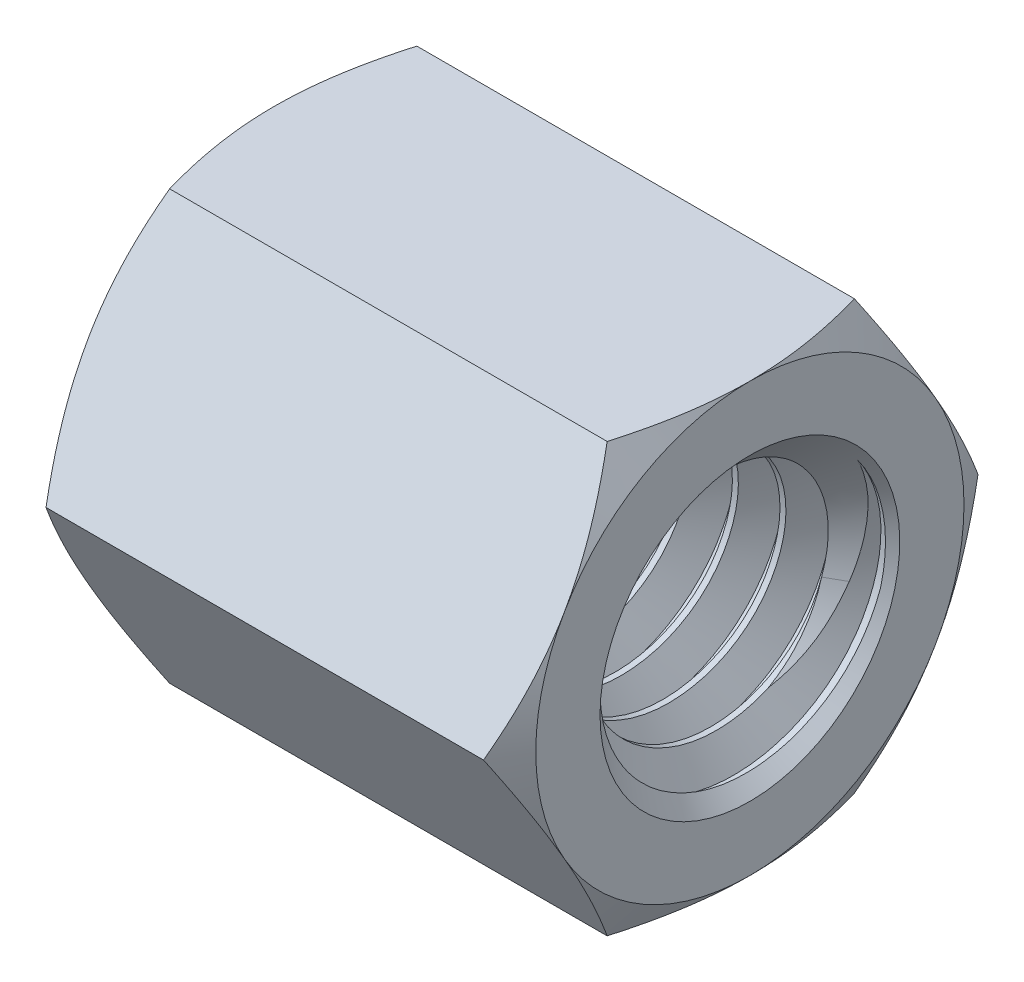
SolidWorks part; units mm, degrees
note: '?' marks a value the reader was unsure of.
ref_plane "Front Plane" through (0, 0, 0) normal (0, 0, 1) x (1, 0, 0)
ref_plane "Top Plane" through (0, 0, 0) normal (0, 1, 0) x (1, 0, 0)
ref_plane "Right Plane" through (0, 0, 0) normal (1, 0, 0) x (0, 0, -1)
sketch "Sketch1" plane through (0, 0, 0) normal (0, 0, 1) x (1, 0, 0)
  line L0 (0, 0) -> (5, 0) construction
  line L1 (0, 2.25) -> (0, -2.25) construction
  line L3 (0, 1.5) -> (-0.5, 1.5) construction
  line L4 (0, 2.25) -> (5, 2.25) construction
  point P6 (0, 0)
  dimension "Hex" = 4.5
  dimension "Pitch" = 0.5
  dimension "Thread OD" = 3
  dimension "Length" = 5
sketch "Sketch2" plane through (0, 0, 0) normal (1, 0, 0) x (0, 0, -1)
  line L0 (0, 0) -> (-1.0607, -1.0607) construction
  line L1 (1.299, 2.25) -> (-1.299, 2.25)
  line L2 (-1.299, 2.25) -> (-2.5981, 0)
  line L3 (-2.5981, 0) -> (-1.299, -2.25)
  line L4 (-1.299, -2.25) -> (1.299, -2.25)
  line L5 (1.299, -2.25) -> (2.5981, 0)
  line L6 (2.5981, 0) -> (1.299, 2.25)
  circle A0 centre (0, 0) radius 2.25 construction
  circle A1 centre (0, 0) radius 1.5 construction
  dimension "D1" = 45
extrude "Boss-Extrude1" add sketch "Sketch2" along normal up to vertex (5 mm away) up to point (5, 0, 0)
sketch "Sketch3" plane through (0, 0, 0) normal (0, 0, 1) x (1, 0, 0)
  line L0 (0, 1.575) -> (0.075, 1.5)
  line L1 (0, 0) -> (5, 0)
  line L2 (0, 0) -> (0, 1.575)
  line L3 (0.075, 1.5) -> (4.925, 1.5)
  line L4 (5, 0) -> (5, 1.575)
  line L9 (0, 2.25) -> (0, -2.25) construction
  line L11 (4.925, 1.5) -> (5, 1.575)
  line L12 (5, 2.25) -> (5, 0) construction
  line L13 (0, 0) -> (5, 0) construction
  line L14 (0, 1.5) -> (-0.5, 1.5) construction
  dimension "D1" = 3.15
  dimension "D2" = 45
revolve "Cut-Revolve1" cut sketch "Sketch3" angle 360 about L13
sketch "Sketch4" plane through (0, 0, 0) normal (-1, 0, 0) x (0, 0, 1)
  circle A0 centre (0, 0) radius 2.25
  circle A1 centre (0, 0) radius 2.25 construction
extrude "Cut-Extrude1" cut sketch "Sketch4" against normal through all draft 60 flip side to cut
sketch "Sketch5" plane through (5, 0, 0) normal (1, 0, 0) x (0, 0, -1)
  circle A0 centre (0, 0) radius 2.25
  circle A1 centre (0, 0) radius 2.25 construction
extrude "Cut-Extrude2" cut sketch "Sketch5" against normal through all draft 60 flip side to cut
ref_axis "Center Axis 1" through (0, 0, 0) along (1, 0, 0)?
sketch "Sketch6" plane through (0, 0, 0) normal (0, 0, 1) x (1, 0, 0)
  line L0 (-0.4278, 1.5) -> (-0.2139, 1.1295) construction
  line L1 (-0.2139, 1.1295) -> (0, 1.5) construction
  line L2 (0, 1.5) -> (-0.4278, 1.5) construction
  line L3 (0, 1.5) -> (-0.5, 1.5) construction
  line L5 (-0.4278, 1.5) -> (-0.4639, 1.5625) construction
  line L6 (-0.4639, 1.5625) -> (0.0361, 1.5625) construction
  line L7 (0.0361, 1.5625) -> (0, 1.5) construction
  line L8 (-0.2452, 1.1836) -> (-0.1827, 1.1836) construction
  line L9 (-0.2139, 1.5) -> (-0.2139, 1.5625) construction
  line L10 (-0.4459, 1.5312) -> (0.018, 1.5312)
  line L11 (0.018, 1.5312) -> (-0.1827, 1.1836)
  line L12 (-0.1827, 1.1836) -> (-0.2452, 1.1836)
  line L13 (-0.2452, 1.1836) -> (-0.4459, 1.5312)
  dimension "D1" = 0.0625
sketch "Sketch7" plane through (0, 0, 0) normal (-1, 0, 0) x (0, 0, 1)
  line L0 (0, 2.25) -> (0, -2.25) construction
  circle A0 centre (0, 0) radius 1.5
curve "Helix/Spiral1" pitch 0.5 height 5.5 turns 11
sweep "Sweep1" add profiles "Sketch6" path "Helix/Spiral1"
sketch "Sketch8" plane through (0, 0, 0) normal (-1, 0, 0) x (0, 0, 1)
  circle A0 centre (0, 0) radius 1.575
extrude "Cut-Extrude3" cut sketch "Sketch8" against normal through all draft 45 and the other way through all draft 45
sketch "Sketch9" plane through (5, 0, 0) normal (1, 0, 0) x (0, 0, -1)
  circle A0 centre (0, 0) radius 1.575
  circle A1 centre (0, 0) radius 1.575 construction
extrude "Cut-Extrude4" cut sketch "Sketch9" against normal through all draft 45 and the other way through all draft 45
equation "\"D1@Sketch3\"=\"Thread OD@Sketch1\"*1.05"
equation "\"D1@Sketch6\"=\"Pitch@Sketch1\"/8"
equation "\"D4@Helix/Spiral1\"=\"Pitch@Sketch1\""
equation "\"D3@Helix/Spiral1\"=\"Pitch@Sketch1\"+\"Length@Sketch1\""
